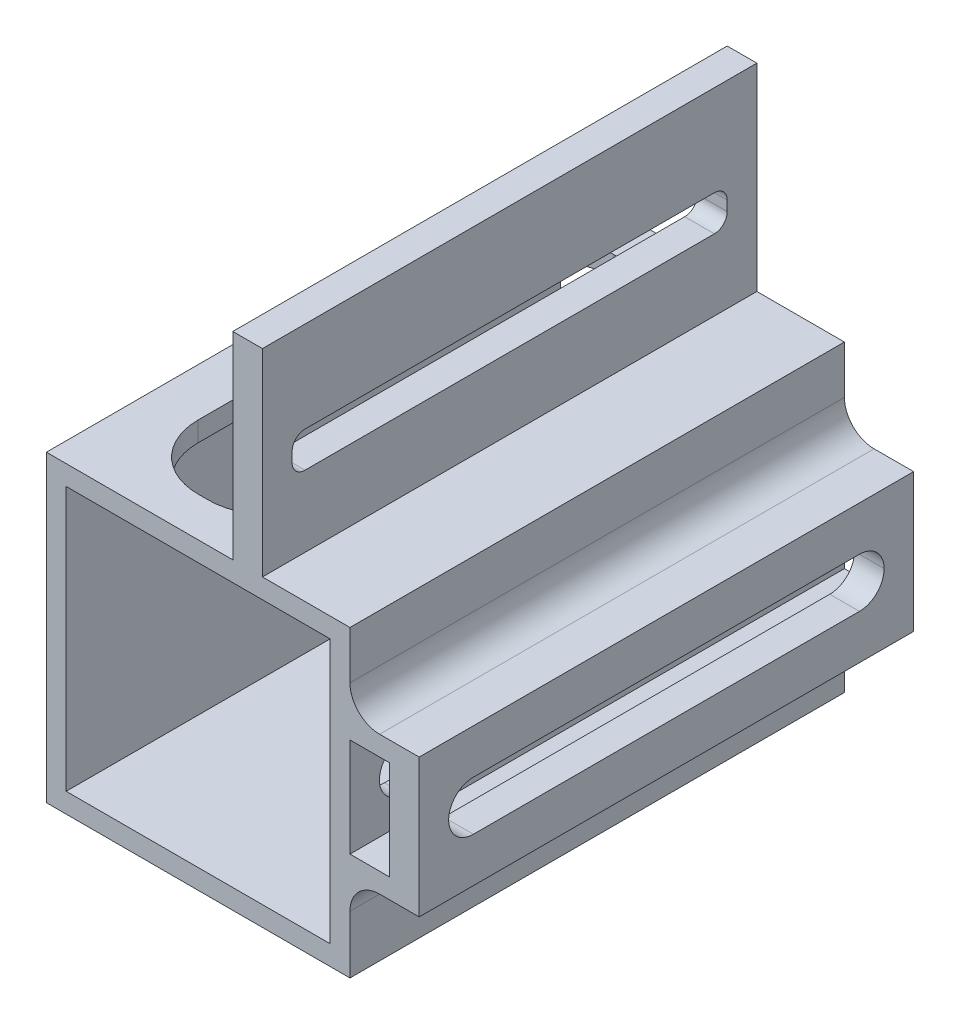
SolidWorks part; units mm, degrees
ref_plane "Alzado" through (0, 0, 0) normal (0, 0, 1) x (1, 0, 0)
ref_plane "Planta" through (0, 0, 0) normal (0, 1, 0) x (1, 0, 0)
ref_plane "Vista lateral" through (0, 0, 0) normal (1, 0, 0) x (0, 0, -1)
sketch "Croquis2" plane through (0, 0, 0) normal (0, 0, 1) x (1, 0, 0)
  line L0 (-51.9511, -1.694) -> (-49.9511, -1.694)
  line L1 (-49.9511, -1.694) -> (-51.9511, -1.694)
  line L2 (-1.9511, -10.694) -> (-1.9511, -41.694)
  line L3 (-1.9511, -41.694) -> (-51.9511, -41.694) construction
  line L4 (-51.9511, -1.694) -> (-51.9511, -41.694) construction
  line L5 (-49.9511, -1.694) -> (-49.9511, -11.294)
  line L6 (-49.9511, -11.294) -> (-36.9511, -11.294)
  line L7 (-36.9511, -11.294) -> (-36.9511, -9.294)
  line L8 (-36.9511, -9.294) -> (-31.9511, -9.294)
  line L9 (-31.9511, -9.294) -> (-31.9511, -11.994)
  line L10 (-31.9511, -11.994) -> (-17.3111, -11.994)
  line L11 (-17.3111, -11.994) -> (-17.3111, -7.694)
  line L12 (-17.3111, -7.694) -> (-24.3111, -7.694)
  line L13 (-24.3111, -7.694) -> (-24.3111, -4.694)
  line L14 (-24.3111, -4.694) -> (-14.3111, -4.694)
  line L15 (-14.3111, -4.694) -> (-14.3111, -10.694)
  line L16 (-14.3111, -10.694) -> (-1.9511, -10.694)
  line L17 (-1.9511, -41.694) -> (-4.5642, -41.694)
  line L18 (-4.5642, -41.694) -> (-4.5642, -19.454)
  line L19 (-4.5642, -19.454) -> (-22.3242, -19.454) construction
  line L20 (-22.3242, -41.694) -> (-22.3242, -15.394) construction
  line L21 (-4.5642, -19.454) -> (-22.3242, -15.394)
  line L22 (-42.1842, -30.694) -> (-40.1642, -30.694)
  line L23 (-22.3242, -15.394) -> (-26.7442, -15.394) construction
  line L24 (-42.1842, -41.694) -> (-42.1842, -30.694) construction
  line L25 (-40.1642, -41.694) -> (-40.1642, -30.694) construction
  line L26 (-26.7442, -15.394) -> (-26.7442, -15.354)
  line L27 (-22.3242, -15.394) -> (-26.7442, -15.354)
  line L28 (-40.1642, -30.694) -> (-26.7442, -15.354) construction
  arc A0 (-40.1642, -30.694) -> (-26.7442, -15.354) centre (-26.4173, -29.1801) cw
  dimension "D1" = 2
  dimension "D2" = 50
  dimension "D3" = 40
  dimension "D4" = 9.6
  dimension "D5" = 13
  dimension "D6" = 2
  dimension "D7" = 5
  dimension "D8" = 2.7
  dimension "D9" = 14.64
  dimension "D10" = 4.3
  dimension "D11" = 3
  dimension "D12" = 10
  dimension "D13" = 6
  dimension "D14" = 12.36
  dimension "D15" = 22.24
  dimension "D16" = 17.76
  dimension "D17" = 26.3
  dimension "D18" = 35.6
  dimension "D19" = 2.02
  dimension "D20" = 11
  dimension "D21" = 4.42
  dimension "D22" = 0.04
sketch "Croquis3" plane through (0, 0, 0) normal (0, 0, 1) x (1, 0, 0)
  line L114 (-15.1572, 8.4809) -> (-41.8572, 8.4809)
  line L133 (-13.1572, 9.4809) -> (-13.1572, 35.1809)
  line L142 (-43.8572, 6.4809) -> (-6.1572, 6.4809)
  line L147 (-27.0072, 35.1809) -> (-27.0072, 37.1809) construction
  line L167 (-43.8572, 37.1809) -> (-27.0072, 37.1809)
  line L182 (-15.1572, 35.1809) -> (-41.8572, 35.1809)
  line L183 (-41.8572, 8.4809) -> (-41.8572, 35.1809)
  line L184 (-15.1572, 8.4809) -> (-15.1572, 35.1809)
  line L190 (-43.8572, 37.1809) -> (-43.8572, 6.4809)
  line L192 (-13.1572, 35.1809) -> (-9.1572, 35.1809)
  line L193 (-9.1572, 35.1809) -> (-9.1572, 9.4809)
  line L194 (-9.1572, 9.4809) -> (-13.1572, 9.4809)
  line L195 (-9.1572, 22.3309) -> (-6.1572, 22.3309) construction
  line L196 (-27.0072, 37.1809) -> (-6.1572, 37.1809)
  line L241 (-6.1572, 37.1809) -> (-6.1572, 6.4809)
  dimension "D5" = 26.7
  dimension "D13" = 3
  dimension "D3" = 2
  dimension "D10" = 37.7
  dimension "D4" = 26.7
  dimension "D6" = 2
  dimension "D7" = 2
  dimension "D8" = 4
  dimension "D12" = 2
  dimension "D28" = 16.85
extrude "Saliente-Extruir1" add sketch "Croquis3" along normal blind 50 contours L196 L241 L142 L190 L167 | L183 L182 L184 L114 | L194 L133 L192 L193
sketch "Croquis14" plane through (-6.1572, 0, 0) normal (1, 0, 0) x (0, 0, -1)
  line L1 (-50, 9.4809) -> (-50, 35.1809) construction
  line L2 (-50, 22.3309) -> (-47.0206, 22.3309) construction
  line L3 (-25, 37.1809) -> (-25, 24.8309) construction
  line L6 (-47.0206, 22.3309) -> (-47.0206, 24.8309)
  line L7 (-47.0206, 24.8309) -> (-2.9794, 24.8309)
  line L8 (-47.0206, 22.3309) -> (-47.0206, 19.8309)
  line L9 (-47.0206, 19.8309) -> (-2.9794, 19.8309)
  line L10 (-2.9794, 22.3309) -> (-2.9794, 19.8309)
  line L11 (-2.9794, 22.3309) -> (-2.9794, 24.8309)
  point P12 (-25, 19.8309)
  dimension "D1" = 2.5
  dimension "D2" = 2.5
extrude "Cortar-Extruir14" cut sketch "Croquis14" against normal up to surface (9 mm away) contours L10 L11 L7 L6 L8 L9 region at (-6.1572, 22.3309, 25) up to face at (-15.1572, 21.8309, 25)
fillet "Redondeo2" radius 2.5 8 edges at (-14.1572, 24.8309, 2.9794) (-7.6572, 24.8309, 2.9794) (-7.6572, 19.8309, 2.9794) (-14.1572, 19.8309, 2.9794) (-14.1572, 24.8309, 47.0206) (-7.6572, 24.8309, 47.0206) (-7.6572, 19.8309, 47.0206) (-14.1572, 19.8309, 47.0206)
sketch "Croquis18" plane through (0, 37.1809, 0) normal (0, 1, 0) x (1, 0, 0)
  line L0 (-28.5072, -4) -> (-28.5072, 0) construction
  line L1 (-25.0072, -46) -> (-32.0072, -46)
  line L2 (-25.0072, -46) -> (-25.0072, -4)
  line L3 (-25.0072, -4) -> (-32.0072, -4)
  line L4 (-15.1572, 0) -> (-41.8572, 0)
  line L5 (-15.1572, -50) -> (-15.1572, 0)
  line L6 (-41.8572, -50) -> (-15.1572, -50)
  line L7 (-41.8572, 0) -> (-41.8572, -50)
  line L8 (-15.1572, 0) -> (-41.8572, 0) construction
  line L9 (-15.1572, -50) -> (-15.1572, 0) construction
  line L10 (-41.8572, -50) -> (-15.1572, -50) construction
  line L11 (-41.8572, 0) -> (-41.8572, -50) construction
  line L12 (-32.0072, -46) -> (-32.0072, -4)
  point P8 (-28.5072, -4)
  point P9 (-28.5072, 0)
  dimension "D2" = 4
  dimension "D3" = 4
  dimension "D4" = 7
  dimension "D1" = 0
extrude "Cortar-Extruir19" cut sketch "Croquis18" against normal up to next
sketch "Croquis19" plane through (0, 0, 0) normal (0, 0, -1) x (-1, 0, 0)
  line L0 (9.1572, 35.1809) -> (9.1572, 9.4809) construction
  line L1 (9.1572, 17.3309) -> (13.1572, 17.3309)
  line L2 (9.1572, 17.3309) -> (9.1572, 15.3309)
  line L3 (9.1572, 15.3309) -> (13.1572, 15.3309)
  line L4 (13.1572, 17.3309) -> (13.1572, 15.3309)
  line L5 (13.1572, 9.4809) -> (13.1572, 35.1809) construction
  line L6 (9.1572, 17.3309) -> (9.1572, 22.3309) construction
  line L7 (9.1572, 22.3309) -> (7.709, 22.3309) construction
  line L8 (13.1572, 27.3309) -> (13.1572, 29.3309)
  line L9 (9.1572, 29.3309) -> (13.1572, 29.3309)
  line L10 (9.1572, 27.3309) -> (9.1572, 29.3309)
  line L11 (9.1572, 27.3309) -> (13.1572, 27.3309)
  line L12 (25.0072, 37.1809) -> (32.0072, 37.1809) construction
  line L13 (25.0072, 37.1809) -> (32.0072, 37.1809) construction
  line L15 (25.0072, 37.1809) -> (22.0072, 37.1809)
  line L16 (25.0072, 37.1809) -> (25.0072, 57.1809)
  line L17 (25.0072, 57.1809) -> (22.0072, 57.1809)
  line L18 (22.0072, 37.1809) -> (22.0072, 57.1809)
  dimension "D1" = 2
  dimension "D2" = 5
  dimension "D3" = 3
  dimension "D4" = 20
extrude "Saliente-Extruir3" add sketch "Croquis19" against normal up to surface (50 mm away) up to face at (-11.1572, 22.3309, 50)
sketch "Croquis20" plane through (-25.0072, 0, 0) normal (-1, 0, 0) x (0, 0, 1)
  line L0 (0, 46.1809) -> (20.5, 46.1809) construction
  line L1 (0, 37.1809) -> (0, 57.1809) construction
  line L2 (20.5, 46.1809) -> (30, 46.1809) construction
  line L3 (30, 46.1809) -> (30, 37.1809) construction
  line L4 (25.25, 46.1809) -> (25.25, 35.1809) construction
  line L5 (3, 44.3809) -> (3, 47.9809)
  line L6 (3, 47.9809) -> (47, 47.9809)
  line L7 (47, 47.9809) -> (47, 44.3809)
  line L8 (50, 57.1809) -> (50, 37.1809) construction
  line L9 (3, 44.3809) -> (47, 44.3809)
  line L10 (30, 37.1809) -> (4, 37.1809) construction
  line L11 (47, 47.9809) -> (47, 50.9809) construction
  line L14 (47, 44.3809) -> (47, 37.1809) construction
  line L15 (46, 35.1809) -> (4, 35.1809) construction
  point P15 (47, 46.1809)
  point P16 (3, 46.1809)
  dimension "D1" = 20.5
  dimension "D2" = 9.5
  dimension "D3" = 3
  dimension "D4" = 3
  dimension "D5" = 3
  dimension "D6" = 1.8
  dimension "D7" = 11
extrude "Cortar-Extruir20" cut sketch "Croquis20" against normal up to next
sketch "Croquis21" plane through (0, 0, 0) normal (0, 0, -1) x (-1, 0, 0)
  line L0 (13.1572, 35.1809) -> (13.1572, 37.1809)
  line L1 (22.0072, 37.1809) -> (6.1572, 37.1809) construction
  line L2 (13.1572, 37.1809) -> (6.1572, 37.1809)
  line L3 (6.1572, 37.1809) -> (6.1572, 29.3309)
  line L4 (6.1572, 37.1809) -> (6.1572, 6.4809) construction
  line L5 (6.1572, 29.3309) -> (9.1572, 29.3309)
  line L6 (9.1572, 29.3309) -> (9.1572, 35.1809)
  line L7 (9.1572, 35.1809) -> (13.1572, 35.1809)
  line L9 (6.1572, 9.4809) -> (6.1572, 15.3309)
  line L10 (6.1572, 15.3309) -> (9.1572, 15.3309)
  line L11 (9.1572, 15.3309) -> (9.1572, 9.4809)
  line L12 (43.8572, 6.4809) -> (6.1572, 6.4809) construction
  line L13 (9.1572, 9.4809) -> (13.1572, 9.4809)
  line L14 (6.1572, 9.4809) -> (6.1572, 6.4809)
  line L15 (6.1572, 6.4809) -> (13.1572, 6.4809)
  line L16 (13.1572, 9.4809) -> (13.1572, 6.4809)
extrude "Cortar-Extruir21" cut sketch "Croquis21" against normal up to next
fillet "Redondeo6" radius 3 2 edges at (-13.1572, 29.3309, 25) (-13.1572, 15.3309, 25)
fillet "Redondeo9" radius 1.3 4 edges at (-23.5072, 44.3809, 3) (-23.5072, 47.9809, 3) (-23.5072, 44.3809, 47) (-23.5072, 47.9809, 47)
sketch "Croquis22" plane through (0, 37.1809, 0) normal (0, 1, 0) x (1, 0, 0)
  line L5 (-32.0072, -46) -> (-25.0072, -46) construction
  line L6 (-32.0072, -4) -> (-39.0072, -4)
  line L7 (-32.0072, -4) -> (-32.0072, -46)
  line L8 (-32.0072, -46) -> (-39.0072, -46)
  line L9 (-39.0072, -4) -> (-39.0072, -46)
  dimension "D1" = 7
extrude "Cortar-Extruir22" cut sketch "Croquis22" against normal up to next
fillet "Redondeo10" radius 6.5 4 edges at (-39.0072, 36.1809, 4) (-25.0072, 36.1809, 4) (-39.0072, 36.1809, 46) (-25.0072, 36.1809, 46)
